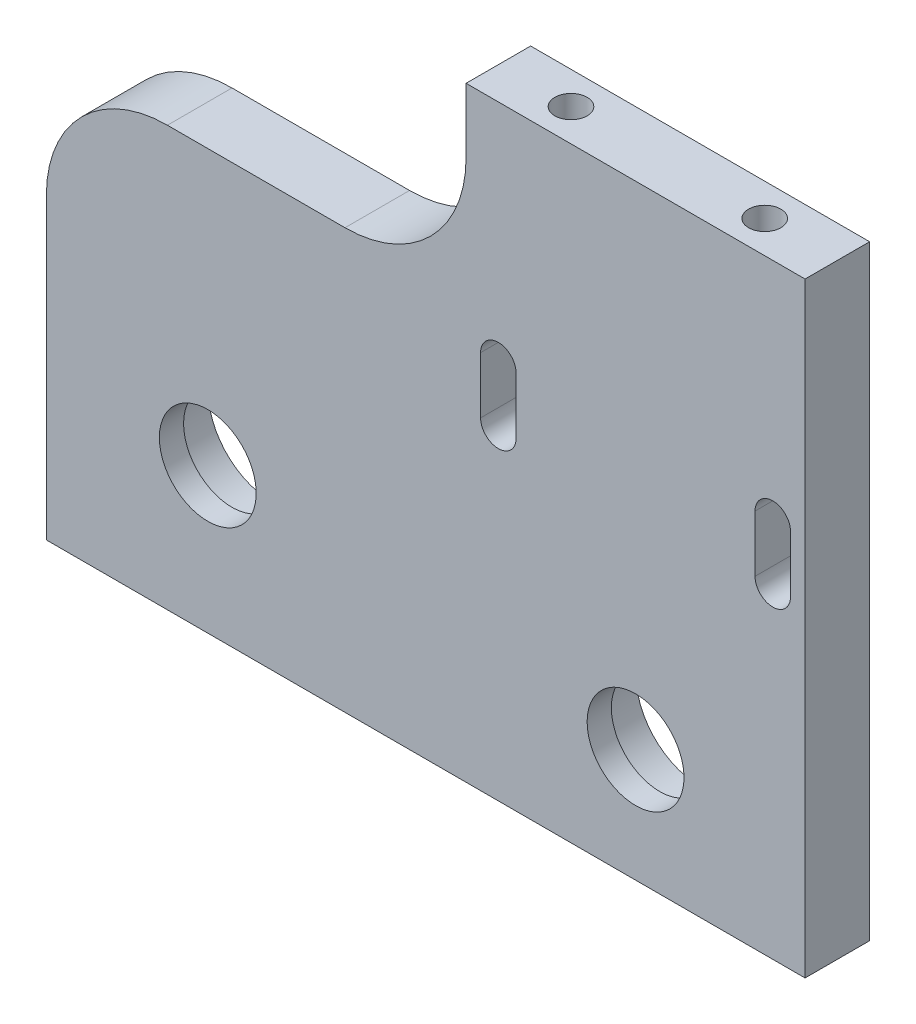
SolidWorks part; units mm, degrees
material "Alliage 1060"
ref_plane "Plan de face" through (0, 0, 0) normal (0, 0, 1) x (1, 0, 0)
ref_plane "Plan de dessus" through (0, 0, 0) normal (0, 1, 0) x (1, 0, 0)
ref_plane "Plan de droite" through (0, 0, 0) normal (1, 0, 0) x (0, 0, -1)
sketch "Esquisse1" plane through (0, 0, 0) normal (0, 0, 1) x (1, 0, 0)
  line L0 (52, 75) -> (52, 52)
  line L1 (0, 0) -> (94, 0)
  line L2 (0, 0) -> (0, 52)
  line L3 (52, 75) -> (94, 75)
  line L4 (94, 0) -> (94, 75)
  line L5 (52, 52) -> (0, 52)
  dimension "D1" = 94
  dimension "D2" = 75
  dimension "D3" = 52
  dimension "D4" = 42
extrude "Boss.-Extru.1" add sketch "Esquisse1" along normal blind 8
sketch "Esquisse2" plane through (0, 0, 0) normal (0, 0, -1) x (-1, 0, 0)
  line L0 (-20, 18) -> (-73, 14) construction
  line L1 (0, 0) -> (-94, 0) construction
  line L2 (0, 52) -> (0, 0) construction
  line L3 (-20, 18) -> (0, 18) construction
  line L4 (-20, 18) -> (-20, 0) construction
  line L5 (-73, 14) -> (-73, 0) construction
  circle A0 centre (-20, 18) radius 7.95
  circle A1 centre (-73, 14) radius 7.95
  dimension "D5" = 15.9
  dimension "D1" = 53
  dimension "D2" = 14
  dimension "D3" = 18
  dimension "D4" = 20
extrude "Enlèv. mat.-Extru.1" cut sketch "Esquisse2" against normal blind 5
sketch "Esquisse3" plane through (0, 0, 5) normal (0, 0, -1) x (-1, 0, 0)
  circle A0 centre (-73, 14) radius 6
  circle A1 centre (-20, 18) radius 6
  dimension "D1" = 12
extrude "Enlèv. mat.-Extru.2" cut sketch "Esquisse3" against normal through all
sketch "Esquisse4" plane through (0, 0, 0) normal (0, 0, -1) x (-1, 0, 0)
  line L0 (-90, 40) -> (-56, 40) construction
  line L1 (-94, 0) -> (-94, 75) construction
  line L2 (0, 0) -> (-94, 0) construction
  line L3 (-90, 40) -> (-90, 47) construction
  line L4 (-92.2, 40) -> (-92.2, 47)
  line L5 (-87.8, 40) -> (-87.8, 47)
  line L6 (-73, 40) -> (-73, 43.5) construction
  line L7 (-56, 40) -> (-56, 47) construction
  line L8 (-53.8, 40) -> (-53.8, 47)
  line L9 (-58.2, 40) -> (-58.2, 47)
  arc A2 (-92.2, 40) -> (-87.8, 40) centre (-90, 40) ccw
  arc A3 (-87.8, 47) -> (-92.2, 47) centre (-90, 47) ccw
  arc A4 (-53.8, 40) -> (-58.2, 40) centre (-56, 40) cw
  arc A5 (-58.2, 47) -> (-53.8, 47) centre (-56, 47) cw
  point P1 (-90, 43.5)
  point P15 (-56, 43.5)
  dimension "D1" = 4.4
  dimension "D2" = 34
  dimension "D3" = 4
  dimension "D4" = 40
  dimension "D5" = 7
extrude "Enlèv. mat.-Extru.3" cut sketch "Esquisse4" against normal through all
sketch "Esquisse5" plane through (0, 75, 0) normal (0, 1, 0) x (1, 0, 0)
  line L0 (94, -8) -> (94, 0) construction
  line L1 (61, -4) -> (85, -4) construction
  line L2 (94, 0) -> (52, 0) construction
  circle A0 centre (61, -4) radius 2
  circle A1 centre (85, -4) radius 2
  point P6 (94, -4)
  point P9 (73, 0)
  point P10 (73, -4)
  dimension "D1" = 4
  dimension "D2" = 9
extrude "Enlèv. mat.-Extru.4" cut sketch "Esquisse5" against normal blind 30
fillet "Congé1" radius 15 2 edges at (0, 52, 4) (52, 52, 4)
sketch "Esquisse6" plane through (0, 0, 0) normal (0, -1, 0) x (1, 0, 0)
  line L0 (6, 4) -> (88, 4) construction
  line L1 (0, 8) -> (94, 8) construction
  line L4 (94, 8) -> (94, 0) construction
  line L5 (0, 8) -> (0, 0) construction
  circle A0 centre (6, 4) radius 2
  circle A1 centre (88, 4) radius 2
  point P6 (47, 8)
  point P7 (47, 4)
  point P12 (0, 4)
  dimension "D1" = 4
  dimension "D2" = 6
extrude "Enlèv. mat.-Extru.5" cut sketch "Esquisse6" against normal blind 20
